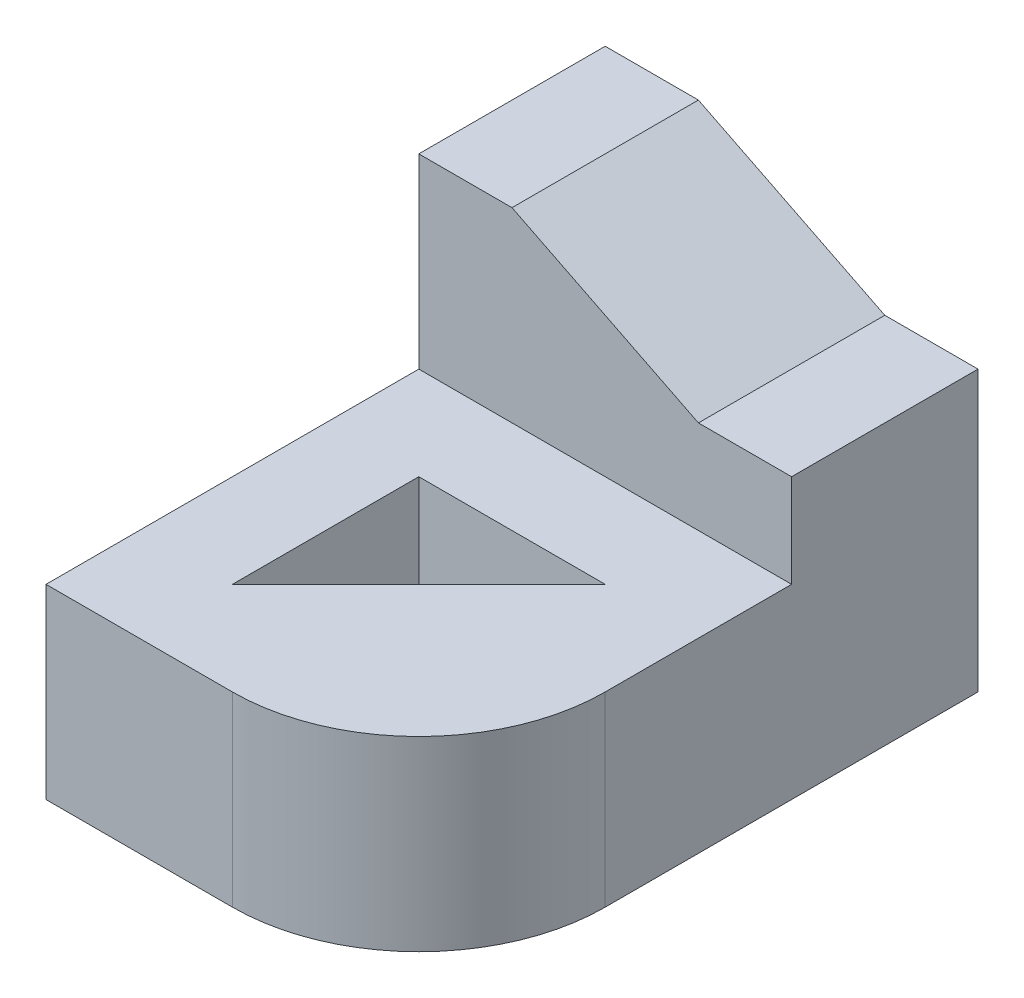
SolidWorks part; units mm, degrees
ref_plane "前基準面" through (0, 0, 0) normal (0, 0, 1) x (1, 0, 0)
ref_plane "上基準面" through (0, 0, 0) normal (0, 1, 0) x (1, 0, 0)
ref_plane "右基準面" through (0, 0, 0) normal (1, 0, 0) x (0, 0, -1)
sketch "草圖1" plane through (0, 0, 0) normal (0, 1, 0) x (1, 0, 0)
  line L0 (5, 5) -> (-5, -5)
  line L1 (-10, 10) -> (10, 10)
  line L2 (-10, 10) -> (-10, -10)
  line L3 (-10, -10) -> (10, -10)
  line L4 (10, 10) -> (10, -10)
  line L5 (-10, 10) -> (10, -10) construction
  line L6 (-10, -10) -> (10, 10) construction
  line L7 (-10, 10) -> (10, 10)
  line L8 (-10, 10) -> (-10, 20)
  line L9 (-10, 20) -> (10, 20)
  line L10 (10, 10) -> (10, 20)
  line L11 (10, 20) -> (5, 20)
  line L12 (10, 20) -> (10, 10)
  line L13 (10, 10) -> (5, 10)
  line L14 (5, 20) -> (5, 10)
  line L15 (-10, 10) -> (-5, 10)
  line L16 (-10, 10) -> (-10, 20)
  line L17 (-10, 20) -> (-5, 20)
  line L18 (-5, 10) -> (-5, 20)
  line L19 (-5, 5) -> (5, 5)
  line L20 (-5, 5) -> (-5, -5)
  line L23 (-5, 5) -> (5, -5) construction
  line L24 (-5, -5) -> (5, 5) construction
  point P0 (0, 0)
  point P12 (0, 0)
  dimension "D1" = 20
  dimension "D2" = 20
  dimension "D3" = 10
  dimension "D4" = 10
  dimension "D5" = 5
  dimension "D6" = 5
  dimension "D7" = 10
extrude "填料-伸長1" add sketch "草圖1" along normal blind 10 contours L4 L7 L1 L2 L3 L20 L19 L0 region at (0.2381, 0, 0.2381)
extrude "填料-伸長2" add sketch "草圖1<3>" along normal blind 20 contours L1 L18 L9 L8 | L18 L7 L14 L9 | L9 L14 L7 L10 region at (-7.5, 0, -15) region at (0, 0, -15) region at (7.5, 0, -15)
sketch "草圖1<3>" plane through (0, 0, 0) normal (0, 1, 0) x (1, 0, 0) same geometry as "草圖1"
sketch "草圖2" plane through (0, 0, -10) normal (0, 0, 1) x (1, 0, 0)
  line L0 (-5, 20) -> (5, 15)
  line L1 (-10, 20) -> (10, 20) construction
  line L2 (5, 15) -> (5, 20)
  line L3 (5, 15) -> (10, 15)
  line L4 (10, 20) -> (10, 10) construction
  line L5 (-5, 20) -> (10, 20)
  line L6 (10, 20) -> (10, 15)
  line M5 (10, 10) -> (10, 20)
  line M6 (10, 20) -> (-10, 20)
  dimension "D1" = 5
  dimension "D2" = 5
  dimension "D3" = 5
extrude "除料-伸長1" cut sketch "草圖2" against normal blind 20 contours L0 L2 M6 | L2 L3 M5 M6 region at (1.6667, 18.3333, -10) region at (7.5, 17.5, -10)
fillet "圓角1" radius 10 1 edges at (10, 5, 10)
scale "縮放比例1" scale about centroid uniform scaling yes scale factor 0.2
